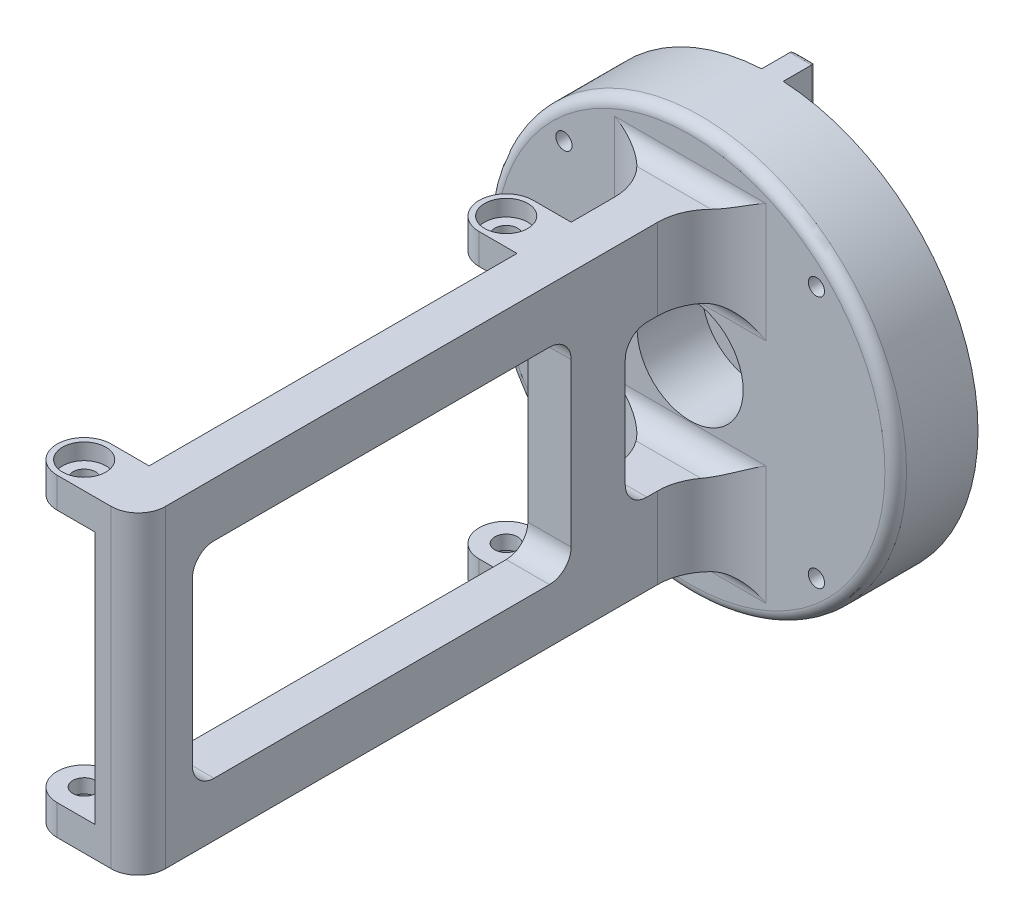
SolidWorks part; units mm, degrees
material "Esun Hard Tough Resin"
ref_plane "Front Plane" through (0, 0, 0) normal (0, 0, 1) x (1, 0, 0)
ref_plane "Top Plane" through (0, 0, 0) normal (0, 1, 0) x (1, 0, 0)
ref_plane "Right Plane" through (0, 0, 0) normal (1, 0, 0) x (0, 0, -1)
sketch "Sketch1" plane through (0, 0, 0) normal (0, 0, 1) x (1, 0, 0)
  line L0 (-11.6673, 11.6673) -> (11.6673, -11.6673) construction
  line L1 (11.6673, 11.6673) -> (-11.6673, -11.6673) construction
  line L2 (0, 16.5) -> (0, -16.5) construction
  circle A0 centre (0, 0) radius 19
  circle A1 centre (0, 0) radius 9 construction
  circle A2 centre (0, 0) radius 16.5 construction
  circle A3 centre (-11.6673, 11.6673) radius 1
  circle A4 centre (11.6673, 11.6673) radius 1
  circle A5 centre (11.6673, -11.6673) radius 1
  circle A6 centre (-11.6673, -11.6673) radius 1
  point P17 (0, 0)
  point P18 (0, 0)
  dimension "D1" = 38
  dimension "D2" = 18
  dimension "D3" = 33
  dimension "D4" = 2
  dimension "D5" = 90
  dimension "D6" = 45
extrude "Boss-Extrude1" add sketch "Sketch1" along normal blind 1.6
sketch "Sketch2" plane through (0, 0, 1.6) normal (0, 0, 1) x (1, 0, 0)
  circle A0 centre (0, 0) radius 19
  circle A1 centre (11.6673, -11.6673) radius 1 construction
  circle A2 centre (11.6673, 11.6673) radius 1 construction
  circle A3 centre (-11.6673, 11.6673) radius 1 construction
  circle A4 centre (-11.6673, -11.6673) radius 1 construction
  circle A5 centre (11.6673, -11.6673) radius 1 construction
  circle A6 centre (11.6673, 11.6673) radius 1 construction
  circle A7 centre (-11.6673, 11.6673) radius 1 construction
  circle A8 centre (-11.6673, -11.6673) radius 1 construction
  circle A9 centre (-11.6673, -11.6673) radius 0.75
  circle A10 centre (-11.6673, 11.6673) radius 0.75
  circle A11 centre (11.6673, 11.6673) radius 0.75
  circle A12 centre (11.6673, -11.6673) radius 0.75
  circle A13 centre (0, 0) radius 19 construction
  dimension "D1" = 1.5
extrude "Boss-Extrude2" add sketch "Sketch2" along normal blind 6
sketch "Sketch8" plane through (0, 0, 0) normal (0, 0, -1) x (-1, 0, 0)
  circle A0 centre (0, 0) radius 12.75
  dimension "D1" = 25.5
extrude "Cut-Extrude4" cut sketch "Sketch8" against normal blind 1
sketch "Sketch3" plane through (0, 0, 7.6) normal (0, 0, 1) x (1, 0, 0)
  circle A0 centre (0, 0) radius 4.9
  dimension "D1" = 9.8
extrude "Cut-Extrude1" cut sketch "Sketch3" against normal offset from surface (6 mm away) 0.6 up to face at (-12.75, 0, 1)
sketch "Sketch4" plane through (0, 0, 0) normal (1, 0, 0) x (0, 0, -1)
  line L0 (-7.6, 14.5) -> (-60.6, 14.5)
  line L1 (-7.6, 19) -> (-7.6, -19) construction
  line L2 (-60.6, 14.5) -> (-60.6, -14.5)
  line L3 (-60.6, -14.5) -> (-7.6, -14.5)
  line L4 (-7.6, -14.5) -> (-7.6, -7)
  line L5 (-7.6, -7) -> (-15.6, -7)
  line L6 (-15.6, -7) -> (-15.6, 7)
  line L7 (-15.6, 7) -> (-7.6, 7)
  line L8 (-7.6, 7) -> (-7.6, 14.5)
  point P6 (-15.6, 0)
  point P11 (-60.6, 0)
  dimension "D1" = 14
  dimension "D2" = 8
  dimension "D3" = 29
  dimension "D4" = 45
extrude "Boss-Extrude3" add sketch "Sketch4" along normal mid plane 4
fillet "Fillet1" radius 5 4 edges at (-2, -10.75, 7.6) (2, -10.75, 7.6) (2, 10.75, 7.6) (-2, 10.75, 7.6)
fillet "Fillet2" radius 2 2 edges at (0, -7, 15.6) (0, 7, 15.6)
ref_plane "Plane1" through (2, 14.5, 12.6) normal (0, 0, 1) x (1, 0, 0)
sketch "Sketch5" plane through (-2, 14.5, 12.6) normal (1, 0, 0) x (0, 0, -1)
  line L0 (0, 0) -> (-48, 0) construction
  line L1 (-48, 0) -> (-43, 0)
  line L2 (-48, 0) -> (-48, -2.8)
  line L3 (-48, -2.8) -> (-43, -2.8)
  line L4 (-43, 0) -> (-43, -2.8)
  line L5 (-9, 0) -> (-4, 0)
  line L6 (-9, 0) -> (-9, -2.8)
  line L7 (-9, -2.8) -> (-4, -2.8)
  line L8 (-4, 0) -> (-4, -2.8)
  line L9 (-1000, -14.5) -> (49000, -14.5) construction
  line L11 (-9, -26.2) -> (-4, -26.2)
  line L12 (-4, -29) -> (-4, -26.2)
  line L13 (-9, -29) -> (-4, -29)
  line L14 (-9, -29) -> (-9, -26.2)
  line L15 (-48, -26.2) -> (-43, -26.2)
  line L16 (-43, -29) -> (-43, -26.2)
  line L17 (-48, -29) -> (-43, -29)
  line L18 (-48, -29) -> (-48, -26.2)
  point P12 (-45.5, -2.8)
  point P17 (-6.5, -2.8)
  dimension "D1" = 39
  dimension "D2" = 5
  dimension "D3" = 2.8
extrude "Boss-Extrude4" add sketch "Sketch5" against normal blind 6
sketch "Sketch6" plane through (0, 14.5, 0) normal (0, 1, 0) x (1, 0, 0)
  line L0 (-8, -55.6) -> (-8, -60.6) construction
  line L1 (-8, -55.6) -> (-8, -60.6) construction
  line L2 (-8, -16.6) -> (-8, -21.6) construction
  line L3 (-8, -16.6) -> (-8, -21.6) construction
  circle A0 centre (-5.5, -58.1) radius 1.05
  circle A1 centre (-5.5, -19.1) radius 1.05
  point P7 (-8, -58.1)
  point P12 (-8, -19.1)
  dimension "D1" = 2.1
  dimension "D2" = 2.5
extrude "Cut-Extrude2" cut sketch "Sketch6" against normal through all
sketch "Sketch7" plane through (0, 14.5, 0) normal (0, 1, 0) x (1, 0, 0)
  circle A0 centre (-5.5, -19.1) radius 2
  circle A1 centre (-5.5, -58.1) radius 2
  dimension "D1" = 4
extrude "Cut-Extrude3" cut sketch "Sketch7" against normal blind 1.5
mirror "Mirror1" about plane through (0, 0, 0) normal (0, 1, 0) of "Cut-Extrude3"
fillet "Fillet3" radius 2.5 8 edges at (-8, -13.1, 60.6) (-8, -13.1, 55.6) (-8, 13.1, 60.6) (-8, 13.1, 55.6) (-8, -13.1, 21.6) (-8, -13.1, 16.6) (-8, 13.1, 21.6) (-8, 13.1, 16.6)
fillet "Fillet4" radius 2.5 1 edges at (2, 0, 60.6)
fillet "Fillet5" radius 1.5 2 edges at (0, -14.5, 7.6) (0, 14.5, 7.6)
fillet "Fillet6" radius 2 2 edges at (0, -7, 7.6) (0, 7, 7.6)
sketch "Sketch9" plane through (0, 0, 0) normal (0, 0, -1) x (-1, 0, 0)
  line L1 (-1, 14.9737) -> (1, 14.9737)
  line L2 (-1, 14.9737) -> (-1, 18.9737)
  line L4 (1, 14.9737) -> (1, 18.9737)
  circle A0 centre (0, 0) radius 19 construction
  circle A1 centre (0, 0) radius 19
  point P7 (0, 14.9737)
  circle M7 centre (0, 0) radius 19
  dimension "D1" = 2
  dimension "D2" = 4
extrude "Boss-Extrude5" add sketch "Sketch9" along normal blind 3 contours L1 L4 L2 M7 region at (0, 16.9825, 0)
fillet "Fillet8" radius 1 1 edges at (19, 0, 7.6)
sketch "Sketch10" plane through (-2, 0, 0) normal (-1, 0, 0) x (0, 0, 1)
  line L0 (20.6, 9.5) -> (20.6, -9.5)
  line L1 (20.6, -9.5) -> (55.6, -9.5)
  line L2 (55.6, -9.5) -> (55.6, 9.5)
  line L3 (55.6, 9.5) -> (20.6, 9.5)
  line L4 (21.6, 14.5) -> (55.6, 14.5) construction
  line L5 (55.6, -14.5) -> (21.6, -14.5) construction
  line L6 (60.6, 11.7) -> (60.6, -11.7) construction
  line L7 (15.6, -5) -> (15.6, 5) construction
  dimension "D1" = 5
  dimension "D2" = 5
  dimension "D3" = 5
  dimension "D4" = 5
extrude "Cut-Extrude5" cut sketch "Sketch10" against normal through all
fillet "Fillet9" radius 2 4 edges at (0, 9.5, 55.6) (0, -9.5, 55.6) (0, -9.5, 20.6) (0, 9.5, 20.6)
fillet "Fillet10" radius 0.4 4 edges at (1, 16.9737, -3) (0, 19, -3) (-1, 16.9737, -3) (0, 14.9737, -3)
equation "\"D2@Sketch10\"=\"D1@Sketch10\""
equation "\"D3@Sketch10\"=\"D1@Sketch10\""
equation "\"D4@Sketch10\"=\"D1@Sketch10\""
